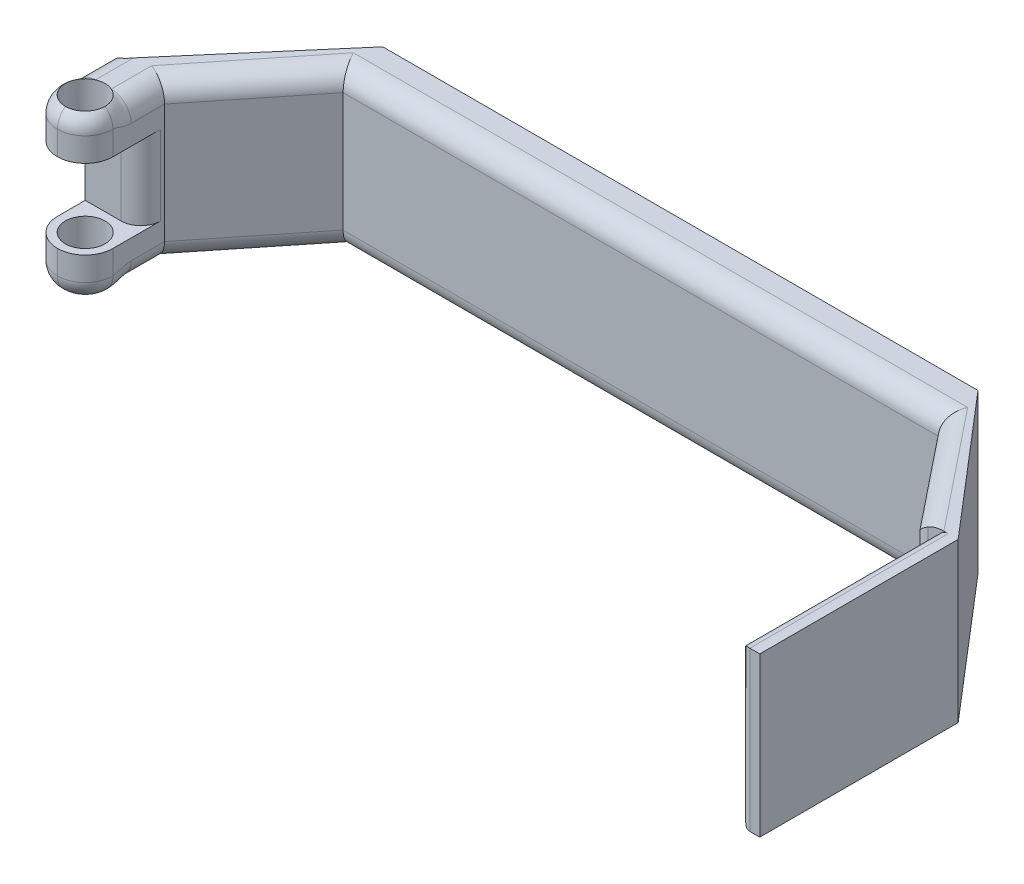
SolidWorks part; units mm, degrees
ref_plane "Front Plane" through (0, 0, 0) normal (0, 0, 1) x (1, 0, 0)
ref_plane "Top Plane" through (0, 0, 0) normal (0, 1, 0) x (1, 0, 0)
ref_plane "Right Plane" through (0, 0, 0) normal (1, 0, 0) x (0, 0, -1)
sketch "Sketch1" plane through (0, 0, 0) normal (0, 1, 0) x (1, 0, 0)
  line L0 (0, 0) -> (20, 25)
  line L1 (20, 25) -> (170, 25)
  line L2 (170, 25) -> (190, 0)
  line L3 (0, 0) -> (-10, 0)
  line L4 (-10, 0) -> (20, 35)
  line L5 (20, 35) -> (170, 35)
  line L6 (190, 0) -> (200, 0)
  line L7 (200, 0) -> (170, 35)
  dimension "D1" = 20
  dimension "D2" = 25
  dimension "D3" = 150
  dimension "D4" = 20
  dimension "D5" = 25
  dimension "D6" = 10
  dimension "D7" = 10
  dimension "D8" = 10
extrude "Boss-Extrude1" add sketch "Sketch1" along normal blind 40
sketch "Sketch2" plane through (0, 0, 0) normal (0, 0, 1) x (1, 0, 0)
  line L1 (0, 40) -> (-14, 40)
  line L2 (0, 40) -> (0, 0)
  line L3 (0, 0) -> (-14, 0)
  line L4 (-14, 40) -> (-14, 0)
  dimension "D1" = 14
extrude "Boss-Extrude2" add sketch "Sketch2" along normal blind 20
sketch "Sketch3" plane through (0, 0, 0) normal (1, 0, 0) x (0, 0, -1)
  line L0 (-20, 0) -> (-20, 40) construction
  line L1 (-20, 30) -> (-6, 30)
  line L2 (-20, 30) -> (-20, 10)
  line L3 (-20, 10) -> (-6, 10)
  line L4 (-6, 30) -> (-6, 10)
  line L5 (-20, 0) -> (0, 0) construction
  dimension "D1" = 14
  dimension "D2" = 20
  dimension "D3" = 10
extrude "Cut-Extrude2" cut sketch "Sketch3" against normal up to next
sketch "Sketch5" plane through (0, 10, 0) normal (0, 1, 0) x (1, 0, 0)
  circle A0 centre (-7, -13) radius 5
  dimension "D1" = 10
extrude "Cut-Extrude3" cut sketch "Sketch5" against normal through all and the other way through all
fillet "Fillet1" radius 7 4 edges at (-14, 5, 20) (0, 5, 20) (0, 35, 20) (-14, 35, 20)
sketch "Sketch7" plane through (0, 0, 0) normal (0, 0, 1) x (1, 0, 0)
  line L0 (190, 0) -> (200, 0) construction
  line L1 (200, 40) -> (195, 40)
  line L2 (200, 40) -> (200, 0)
  line L3 (200, 0) -> (195, 0)
  line L4 (195, 40) -> (195, 0)
extrude "Boss-Extrude3" add sketch "Sketch7" along normal blind 50
fillet "Fillet2" radius 5 12 edges at (0, 0, 6.5) (-14, 0, 6.5) (-14, 40, 6.5) (0, 40, 6.5) (0, 20, 6) (190, 20, 0) (180, 40, -12.5) (180, 0, -12.5) (95, 0, -25) (10, 0, -12.5) (95, 40, -25) (10, 40, -12.5)
fillet "Fillet3" radius 2.5 3 edges at (195, 20, 50) (195, 0, 24.123) (195, 40, 24.123)
